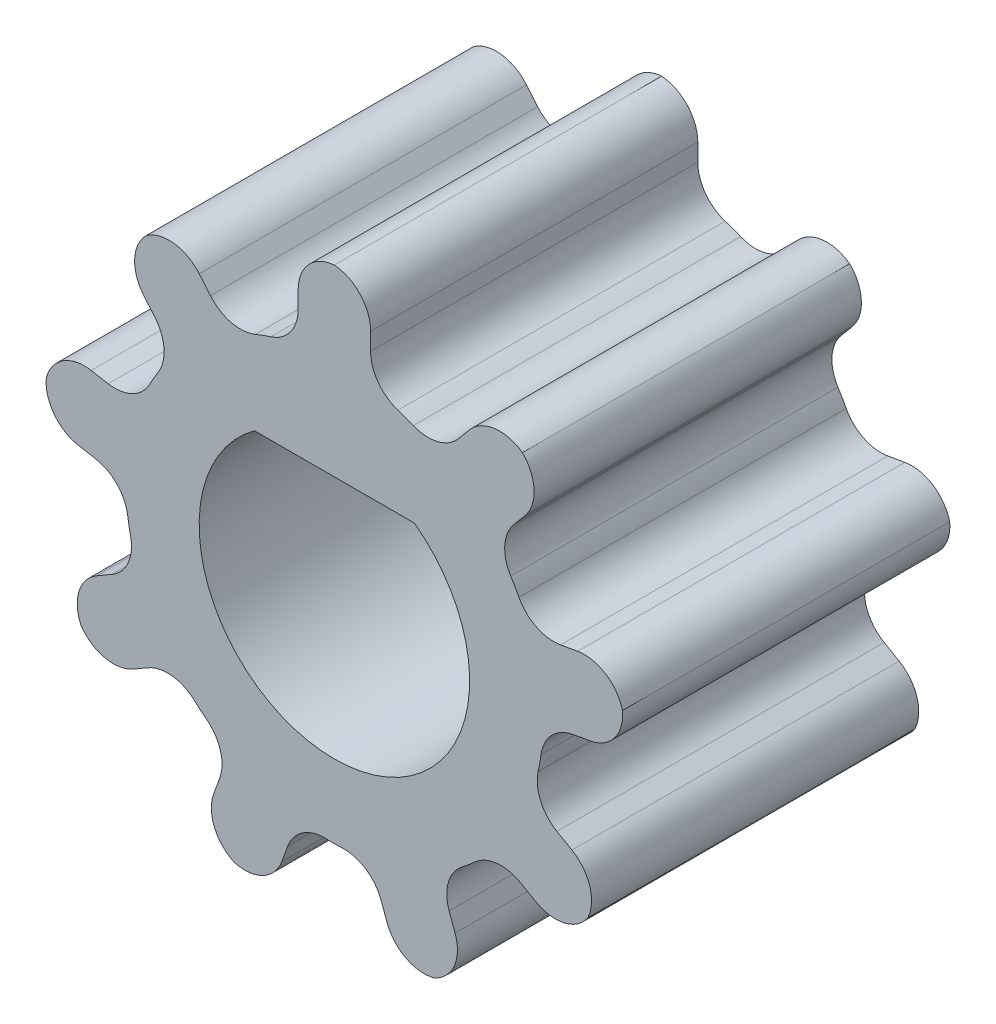
SolidWorks part; units mm, degrees
ref_plane "Front Plane" through (0, 0, 0) normal (0, 0, 1) x (1, 0, 0)
ref_plane "Top Plane" through (0, 0, 0) normal (0, 1, 0) x (1, 0, 0)
ref_plane "Right Plane" through (0, 0, 0) normal (1, 0, 0) x (0, 0, -1)
sketch "Sketch1" plane through (0, 0, 0) normal (0, 0, 1) x (1, 0, 0)
  line L1 (1.8308, 1.5362) -> (1.1949, 2.0697) construction
  line L2 (1.1949, 2.0697) -> (0.415, 2.3536) construction
  line L3 (0.415, 2.3536) -> (-0.415, 2.3536) construction
  line L4 (-0.415, 2.3536) -> (-1.1949, 2.0697) construction
  line L5 (-1.1949, 2.0697) -> (-1.8308, 1.5362) construction
  line L6 (-1.8308, 1.5362) -> (-2.2458, 0.8174) construction
  line L7 (-2.2458, 0.8174) -> (-2.3899, 0) construction
  line L8 (-2.3899, 0) -> (-2.2458, -0.8174) construction
  line L9 (-2.2458, -0.8174) -> (-1.8308, -1.5362) construction
  line L10 (-1.8308, -1.5362) -> (-1.1949, -2.0697) construction
  line L11 (-1.1949, -2.0697) -> (-0.415, -2.3536) construction
  line L12 (-0.415, -2.3536) -> (0.415, -2.3536) construction
  line L13 (0.415, -2.3536) -> (1.1949, -2.0697) construction
  line L14 (1.1949, -2.0697) -> (1.8308, -1.5362) construction
  line L15 (1.8308, -1.5362) -> (2.2458, -0.8174) construction
  line L16 (2.2458, -0.8174) -> (2.3899, 0) construction
  line L17 (2.3899, 0) -> (2.2458, 0.8174) construction
  line L18 (2.2458, 0.8174) -> (1.8308, 1.5362) construction
  circle A0 centre (0, 0) radius 1.55
  circle A1 centre (0, 0) radius 2.3899
  circle A2 centre (0, 0) radius 2.3536 construction
  dimension "D1" = 3.1
  dimension "D3" = 0.83
extrude "Boss-Extrude1" add sketch "Sketch1" along normal blind 3.75
sketch "Sketch2" plane through (0, 0, 3.75) normal (0, 0, 1) x (1, 0, 0)
  line L0 (-0.415, 2.3536) -> (-0.415, 3.3536)
  line L1 (-0.415, 3.3536) -> (0.415, 3.3536)
  line L2 (0.415, 3.3536) -> (0.415, 2.3536)
  line L3 (0.415, 2.3536) -> (-0.415, 2.3536)
  circle A0 centre (0, 0) radius 2.3899 construction
  dimension "D1" = 1
  dimension "D2" = 0.83
extrude "Boss-Extrude2" add sketch "Sketch2" against normal up to surface (3.75 mm away) up to face at (2.3899, 0, 0)
ref_axis "Axis1" through (0, 0, 3.75) along (0, 0, -1)
fillet "Fillet1" radius 0.45 4 edges at (-0.415, 2.3536, 1.875) (-0.415, 3.3536, 1.875) (0.415, 2.3536, 1.875) (0.415, 3.3536, 1.875)
pattern_circular "CirPattern1" count 9 every 40 about axis through (0, 0, 3.75) along (0, 0, -1) of "Fillet1", "Boss-Extrude2"
sketch "Sketch3" plane through (0, 0, 0) normal (0, 0, -1) x (-1, 0, 0)
  line L1 (0.9165, 1.25) -> (-0.9165, 1.25)
  line L2 (0.9165, 1.25) -> (0.9165, 1.55)
  line L3 (0.9165, 1.55) -> (-0.9165, 1.55)
  line L4 (-0.9165, 1.25) -> (-0.9165, 1.55)
  circle A0 centre (0, 0) radius 1.55 construction
  circle A1 centre (0, 0) radius 1.5 construction
  dimension "D1" = 3
  dimension "D2" = 1.25
extrude "Boss-Extrude3" add sketch "Sketch3" against normal up to surface (3.75 mm away) up to face at (0, 0, 3.75)
